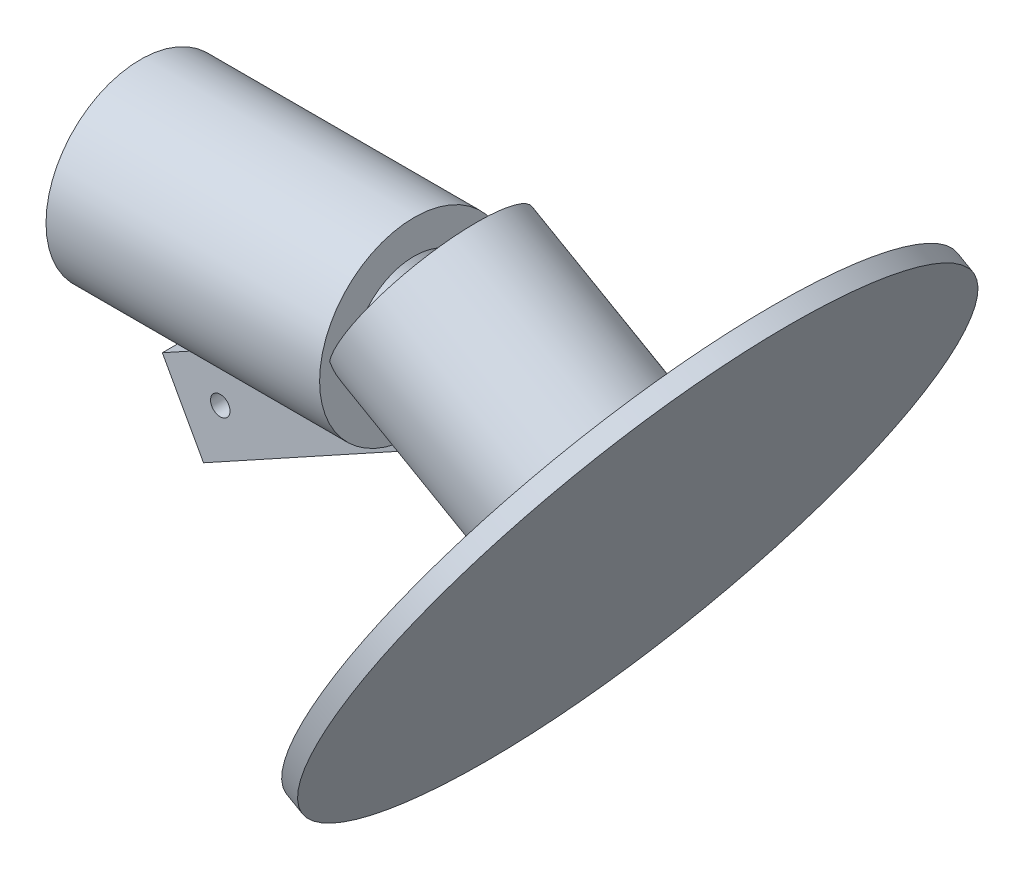
SolidWorks part; units mm, degrees
ref_plane "Front Plane" through (0, 0, 0) normal (0, 0, 1) x (1, 0, 0)
ref_plane "Top Plane" through (0, 0, 0) normal (0, 1, 0) x (1, 0, 0)
ref_plane "Right Plane" through (0, 0, 0) normal (1, 0, 0) x (0, 0, -1)
sketch "Pad And Pedestal Sketch" plane through (0, 0, 0) normal (0, 0, 1) x (1, 0, 0)
  line L0 (1511.9684, -29.7968) -> (1407.8118, 29.7968) construction
  line L1 (1481.5894, -12.4153) -> (1506.42, 30.9833)
  line L2 (1506.42, 30.9833) -> (1503.8161, 32.4731)
  line L3 (1503.8161, 32.4731) -> (1486.4347, 2.0941)
  line L4 (1486.4347, 2.0941) -> (1455.1877, 19.9722)
  line L5 (1455.1877, 19.9722) -> (1453.6978, 17.3682)
  line L6 (1453.6978, 17.3682) -> (1482.3409, 0.98)
  line L7 (1482.3409, 0.98) -> (1476.3816, -9.4356)
  line L8 (1476.3816, -9.4356) -> (1481.5894, -12.4153)
revolve "Pad And Pedestal" add sketch "Pad And Pedestal Sketch" angle 360 about L0
ref_axis "Engine Axis" through (1511.741, 0, 0) along (-1, 0, 0)
sketch "Socket Sketch" plane through (0, 0, 0) normal (0, 0, 1) x (1, 0, 0)
  line L0 (-3000, 0) -> (3000, 0) construction
  line L1 (1400, 13.45) -> (1400, 15.5)
  line L2 (1400, 15.5) -> (1444.8901, 15.5)
  line L3 (1444.8901, 15.5) -> (1444.8901, 10)
  line L4 (1444.8901, 10) -> (1430, 10)
  line L5 (1430, 10) -> (1430, 0)
  line L6 (1430, 0) -> (1425, 0)
  line L7 (1425, 0) -> (1425, 13.45)
  line L8 (1425, 13.45) -> (1400, 13.45)
revolve "Socket" add sketch "Socket Sketch" angle 360 about L0
sketch "Tab Sketch" plane through (0, 0, 0) normal (0, 0, 1) x (1, 0, 0)
  line L0 (1465.0196, -5.1661) -> (1413.3427, -33.6353)
  line L1 (1413.3427, -33.6353) -> (1406.5873, -21.373)
  line L2 (1406.5873, -21.373) -> (1458.2642, 7.0962)
  line L3 (1458.2642, 7.0962) -> (1465.0196, -5.1661)
extrude "Tab" add sketch "Tab Sketch" along normal mid plane 6
sketch "Cable Pin Hole Sketch" plane through (0, 0, 0) normal (0, 0, 1) x (1, 0, 0)
  circle A0 centre (1416.0961, -24.1265) radius 1.6
extrude "Cable Pin Hole" cut sketch "Cable Pin Hole Sketch" against normal mid plane 12
sketch "Bore Clear Sketch" plane through (0, 0, 0) normal (0, 0, 1) x (1, 0, 0)
  line L0 (-3000, 0) -> (3000, 0) construction
  line L1 (1399, 0) -> (1425, 0)
  line L2 (1425, 0) -> (1425, 13.45)
  line L3 (1425, 13.45) -> (1399, 13.45)
  line L4 (1399, 13.45) -> (1399, 0)
revolve "Bore Clear" cut sketch "Bore Clear Sketch" angle 360 about L0
